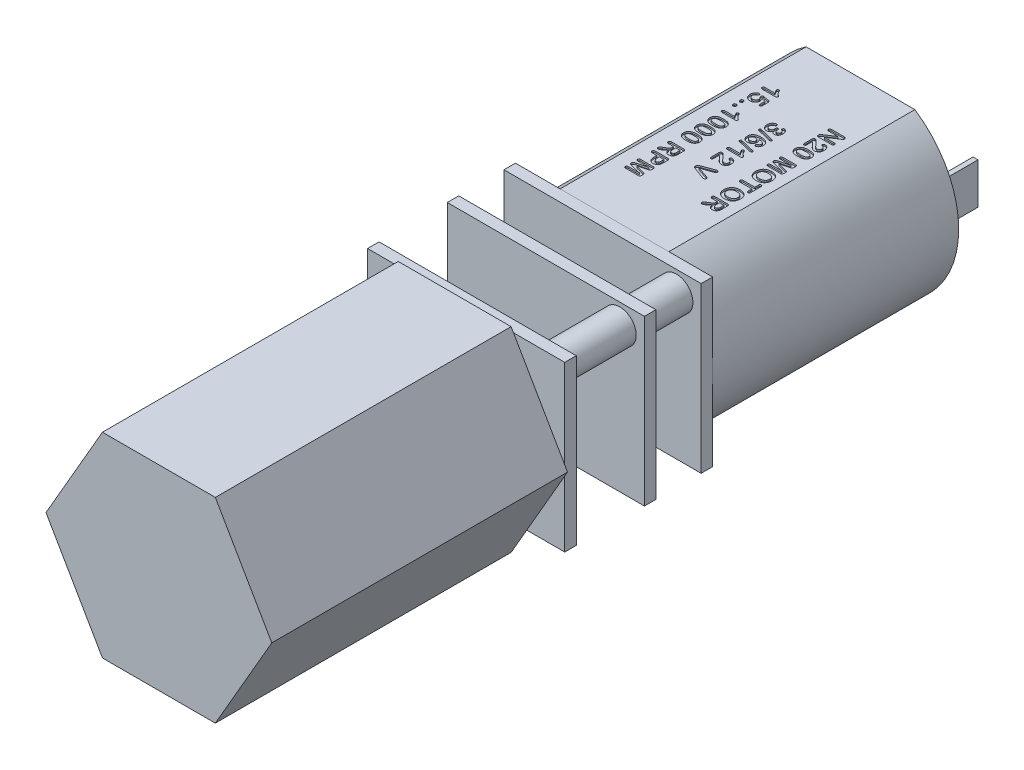
SolidWorks part; units mm, degrees
ref_plane "Front Plane" through (0, 0, 0) normal (0, 0, 1) x (1, 0, 0)
ref_plane "Top Plane" through (0, 0, 0) normal (0, 1, 0) x (1, 0, 0)
ref_plane "Right Plane" through (0, 0, 0) normal (1, 0, 0) x (0, 0, -1)
sketch "Sketch1" plane through (0, 0, 0) normal (0, 0, 1) x (1, 0, 0)
  line L0 (-6, 0) -> (6, 0) construction
  line L1 (-6, -5) -> (6, -5)
  line L2 (-6, -5) -> (-6, 5)
  line L3 (-6, 5) -> (6, 5)
  line L4 (6, -5) -> (6, 5)
  line L5 (-6, -5) -> (6, 5) construction
  line L6 (-6, 5) -> (6, -5) construction
  line L7 (-1.118, 1) -> (1.118, 1)
  line L8 (0, 5) -> (0, -5) construction
  line L9 (-3.3091, 4.975) -> (3.3091, 4.975)
  line L10 (-3.3091, -4.975) -> (3.3091, -4.975)
  line L11 (-4, 1.25) -> (-4, -1.25) construction
  line L12 (3.85, 1.25) -> (4.15, 1.25)
  line L13 (3.85, 1.25) -> (3.85, -1.25)
  line L14 (3.85, -1.25) -> (4.15, -1.25)
  line L15 (4.15, 1.25) -> (4.15, -1.25)
  line L16 (3.85, 1.25) -> (4.15, -1.25) construction
  line L17 (3.85, -1.25) -> (4.15, 1.25) construction
  line L18 (-4.15, 1.25) -> (-3.85, 1.25)
  line L19 (-4.15, 1.25) -> (-4.15, -1.25)
  line L20 (-4.15, -1.25) -> (-3.85, -1.25)
  line L21 (-3.85, 1.25) -> (-3.85, -1.25)
  line L22 (-4.15, 1.25) -> (-3.85, -1.25) construction
  line L23 (-4.15, -1.25) -> (-3.85, 1.25) construction
  line L24 (4, 1.25) -> (4, -1.25) construction
  arc A0 (-1.118, 1) -> (1.118, 1) centre (0, 0) ccw
  circle A1 centre (0, 0) radius 2
  circle A2 centre (-4.5, 0) radius 0.5
  circle A3 centre (4.5, 0) radius 0.5
  circle A4 centre (-4.5, -3.75) radius 1
  circle A5 centre (4.5, 3.75) radius 1
  arc A6 (3.3091, -4.975) -> (3.3091, 4.975) centre (0, 0) ccw
  arc A7 (-3.3091, 4.975) -> (-3.3091, -4.975) centre (0, 0) ccw
  circle A8 centre (0, 0) radius 2.5
  point P0 (0, 0)
  point P26 (4, 0)
  point P32 (-4, 0)
  dimension "D1" = 3
  dimension "D2" = 4
  dimension "D6" = 9
  dimension "D7" = 1
  dimension "D8" = 2
  dimension "D9" = 9
  dimension "D11" = 11.95
  dimension "D13" = 5
  dimension "D3" = 12
  dimension "D4" = 10
  dimension "D5" = 1
  dimension "D10" = 4.5
  dimension "D12" = 9.95
  dimension "D14" = 0.3
  dimension "D15" = 2.5
  dimension "D16" = 8
extrude "Boss-Extrude1" add sketch "Sketch1" along normal blind 0.7 contours A1
extrude "Boss-Extrude2" add sketch "Sketch1<3>" along normal blind 10.7 contours A0 L7
sketch "Sketch1<3>" plane through (0, 0, 0) normal (0, 0, 1) x (1, 0, 0) same geometry as "Sketch1"
extrude "Boss-Extrude3" add sketch "Sketch1<5>" against normal blind 0.7 contours L4 L3 L2 L1
sketch "Sketch1<5>" plane through (0, 0, 0) normal (0, 0, 1) x (1, 0, 0) same geometry as "Sketch1"
extrude "Boss-Extrude4" add sketch "Sketch1<6>" against normal blind 0.7 from offset 4.85 separate body contours L3 L4 L1 L2 offset against normal yes
sketch "Sketch1<6>" plane through (0, 0, 0) normal (0, 0, 1) x (1, 0, 0) same geometry as "Sketch1"
extrude "Boss-Extrude5" add sketch "Sketch1<7>" against normal blind 0.7 from offset 8.3 separate body contours L3 L4 L1 L2 offset against normal yes
sketch "Sketch1<7>" plane through (0, 0, 0) normal (0, 0, 1) x (1, 0, 0) same geometry as "Sketch1"
extrude "Boss-Extrude6" add sketch "Sketch1<8>" against normal up to surface (9 mm away) contours A4 | A5 up to face at (0, 0, -9)
sketch "Sketch1<8>" plane through (0, 0, 0) normal (0, 0, 1) x (1, 0, 0) same geometry as "Sketch1"
extrude "Boss-Extrude7" add sketch "Sketch1<9>" against normal blind 15 from surface contours A6 L9 A7 L10 starting at face at (0, 0, -9)
sketch "Sketch1<9>" plane through (0, 0, 0) normal (0, 0, 1) x (1, 0, 0) same geometry as "Sketch1"
extrude "Boss-Extrude8" add sketch "Sketch1<10>" against normal blind 0.7 from surface contours A8 starting at face at (0, 0, -24)
sketch "Sketch1<10>" plane through (0, 0, 0) normal (0, 0, 1) x (1, 0, 0) same geometry as "Sketch1"
extrude "Boss-Extrude9" add sketch "Sketch1<11>" against normal blind 3 from surface contours L15 L14 L13 L12 | L21 L20 L19 L18 starting at face at (-2.5, 0, -24)
sketch "Sketch1<11>" plane through (0, 0, 0) normal (0, 0, 1) x (1, 0, 0) same geometry as "Sketch1"
sketch "Sketch2" plane through (0, 4.975, 0) normal (0, 1, 0) x (1, 0, 0)
  line L0 (1.7257, 24) -> (1.7257, 9) construction
  line L1 (3.3091, 24) -> (-3.3091, 24) construction
  line L2 (3.3091, 9) -> (-3.3091, 9) construction
  text T0 "N20 MOTOR\r\n3/6/12 V\r\n15..1000 RPM" font "Arial Rounded MT Bold" height 1
extrude "Cut-Extrude1" cut sketch "Sketch2" against normal blind 0.1
hole_wizard "M1.6 Tapped Hole1" positions "Sketch3" profile "Sketch4" tap size "M1.6" standard "DIN" end condition up to next
sketch "Sketch3" plane through (0, 0, 0) normal (0, 0, 1) x (1, 0, 0)
  point P0 (4.5, 0)
  point P2 (-4.5, 0)
sketch "Sketch4" plane through (4.5, 0, 0) normal (1, 0, 0) x (0, -1, 0)
  line L0 (0, 0) -> (0, 0.7)
  line L1 (0, 0.7) -> (0.625, 0.7)
  line L2 (0.625, 0.7) -> (0.625, 0)
  line L5 (0.625, 0) -> (0, 0)
  line L11 (0, -6.35) -> (0, 107.95) construction
  dimension "Thru Tap Drill Dia." = 1.25
  dimension "Thru Tap Drill Depth" = 0.7
cosmetic thread "Hole Thread1" parameters "D2"=1.6
cosmetic thread "Hole Thread2" parameters "D2"=1.6
sketch "Croquis1" plane through (0, 0, 10.7) normal (0, 0, 1) x (1, 0, 0)
  line L1 (6.8705, 0) -> (3.4352, 5.95)
  line L2 (3.4352, 5.95) -> (-3.4352, 5.95)
  line L3 (-3.4352, 5.95) -> (-6.8705, 0)
  line L4 (-6.8705, 0) -> (-3.4352, -5.95)
  line L5 (-3.4352, -5.95) -> (3.4352, -5.95)
  line L6 (3.4352, -5.95) -> (6.8705, 0)
  circle A0 centre (0, 0) radius 5.95 construction
  dimension "D1" = 11.9
extrude "Saliente-Extruir1" add sketch "Croquis1" against normal blind 10 and the other way blind 8 contours L1 L2 L3 L4 L5 L6
